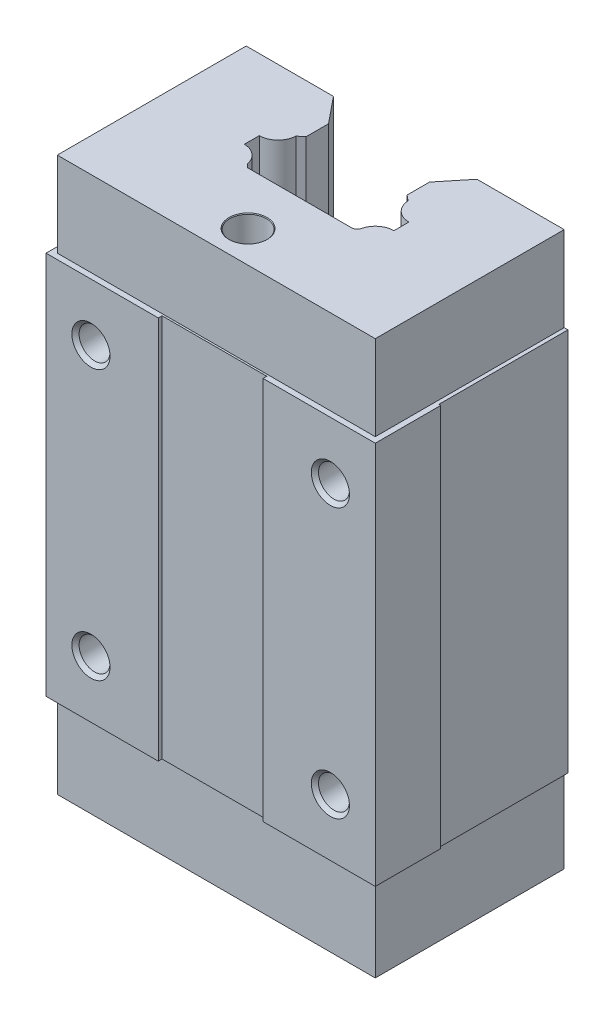
SolidWorks part; units mm, degrees
material "5086-H32, Stange (SS)"
ref_plane "Ebene vorne" through (0, 0, 0) normal (0, 0, 1) x (1, 0, 0)
ref_plane "Ebene oben" through (0, 0, 0) normal (0, 1, 0) x (1, 0, 0)
ref_plane "Ebene rechts" through (0, 0, 0) normal (1, 0, 0) x (0, 0, -1)
ref_plane "Ebene1" through (0, 0, 4) normal (0, 0, -1) x (-1, 0, 0)
sketch "Skizze1" plane through (0, 0, 4) normal (0, 0, -1) x (-1, 0, 0)
  line L0 (-22, -25.65) -> (22, -25.65)
  line L1 (22, -25.65) -> (22, 25.65)
  line L2 (22, 25.65) -> (-22, 25.65)
  line L3 (-22, 25.65) -> (-22, -25.65)
extrude "Aufsatz-Linear austragen1" add sketch "Skizze1" against normal blind 26
sketch "Skizze2" plane through (0, -25.65, 0) normal (0, -1, 0) x (1, 0, 0)
  line L0 (-21.75, 4) -> (-21.75, 21.25)
  line L1 (-21.75, 21.25) -> (-22, 21.25)
  line L2 (-22, 21.25) -> (-22, 4)
  line L3 (-22, 4) -> (-21.75, 4)
extrude "Schnitt-Linear austragen1" cut sketch "Skizze2" against normal through all
sketch "Skizze3" plane through (0, -25.65, 0) normal (0, -1, 0) x (1, 0, 0)
  line L0 (7, 30) -> (-7, 30)
  line L1 (-7, 30) -> (-7, 29.5)
  line L2 (-7, 29.5) -> (7, 29.5)
  line L3 (7, 29.5) -> (7, 30)
extrude "Schnitt-Linear austragen2" cut sketch "Skizze3" against normal through all
sketch "Skizze4" plane through (0, -25.65, 0) normal (0, -1, 0) x (1, 0, 0)
  line L0 (22, 21.25) -> (21.75, 21.25)
  line L1 (21.75, 21.25) -> (21.75, 4)
  line L2 (21.75, 4) -> (22, 4)
  line L3 (22, 4) -> (22, 21.25)
extrude "Schnitt-Linear austragen3" cut sketch "Skizze4" against normal blind 51.3
sketch "Skizze5" plane through (0, 25.65, 0) normal (0, 1, 0) x (-1, 0, 0)
  line L0 (21.25, 4) -> (-21.25, 4)
  line L1 (-21.25, 4) -> (-21.25, 29.25)
  line L2 (-21.25, 29.25) -> (21.25, 29.25)
  line L3 (21.25, 29.25) -> (21.25, 4)
extrude "Aufsatz-Linear austragen2" add sketch "Skizze5" along normal blind 11.35
sketch "Skizze6" plane through (0, -25.65, 0) normal (0, -1, 0) x (1, 0, 0)
  line L0 (21.25, 4) -> (-21.25, 4)
  line L1 (-21.25, 4) -> (-21.25, 29.25)
  line L2 (-21.25, 29.25) -> (21.25, 29.25)
  line L3 (21.25, 29.25) -> (21.25, 4)
extrude "Aufsatz-Linear austragen3" add sketch "Skizze6" along normal blind 11.35
sketch "Skizze7" plane through (0, -37, 0) normal (0, -1, 0) x (1, 0, 0)
  line L0 (-9.5938, 4) -> (9.5938, 4)
  line L1 (9.5938, 4) -> (6.75, 7.5)
  line L2 (6.75, 7.5) -> (6.75, 10.5)
  line L3 (6.75, 10.5) -> (7.5, 11.1094)
  line L4 (10, 13.5) -> (10, 15.5)
  line L5 (7.5, 18) -> (-7.5, 18)
  line L6 (-10, 15.5) -> (-10, 13.5)
  line L7 (-7.5, 11.1094) -> (-6.75, 10.5)
  line L8 (-6.75, 10.5) -> (-6.75, 7.5)
  line L9 (-6.75, 7.5) -> (-9.5938, 4)
  arc A0 (7.5, 11.1094) -> (10, 13.5) centre (10, 10.9975) cw
  arc A1 (10, 15.5) -> (7.5, 18) centre (10, 18) cw
  arc A2 (-7.5, 18) -> (-10, 15.5) centre (-10, 18) cw
  arc A3 (-10, 13.5) -> (-7.5, 11.1094) centre (-10, 10.9975) cw
extrude "Schnitt-Linear austragen4" cut sketch "Skizze7" against normal through all
hole_wizard "Bohrung1" positions "Skizze9" profile "Skizze8" legacy
sketch "Skizze9" plane through (0, -37, 0) normal (0, -1, 0) x (-1, 0, 0)
  point P0 (0, -25)
sketch "Skizze8" plane through (0, -37, 25) normal (1, 0, 0) x (0, 0, -1)
  line L0 (0, 0) -> (0, 16.4772)
  line L1 (0, 16.4772) -> (2.4585, 15)
  line L2 (2.4585, 15) -> (2.4585, 0)
  line L4 (2.4585, 0) -> (0, 0)
  line L6 (0, 16.4772) -> (-2.4585, 15) construction
  line L7 (0, -4.2442) -> (0, 117.3081) construction
  dimension "Durchmesser" = 4.917
  dimension "Tiefe" = 15
  dimension "Spitzenwinkel" = 118
hole_wizard "Bohrung2" positions "Skizze11" profile "Skizze10" legacy
sketch "Skizze11" plane through (0, 37, 0) normal (0, 1, 0) x (1, 0, 0)
  point P0 (0, -25)
sketch "Skizze10" plane through (0, 37, 25) normal (1, 0, 0) x (0, 0, 1)
  line L0 (0, 0) -> (0, 16.4772)
  line L1 (0, 16.4772) -> (2.4585, 15)
  line L2 (2.4585, 15) -> (2.4585, 0)
  line L4 (2.4585, 0) -> (0, 0)
  line L6 (0, 16.4772) -> (-2.4585, 15) construction
  line L7 (0, -4.2442) -> (0, 117.3081) construction
  dimension "Durchmesser" = 4.917
  dimension "Tiefe" = 15
  dimension "Spitzenwinkel" = 118
hole_wizard "Durchgangsloch für M3.51" positions "Skizze13" profile "Skizze12" hole size "M3.5" standard "ANSI Metrisch"
sketch "Skizze13" plane through (0, 0, 30) normal (0, 0, 1) x (1, 0, 0)
  point P0 (16, -18)
  point P1 (16, 18)
  point P2 (-16, 18)
  point P3 (-16, -18)
sketch "Skizze12" plane through (16, -18, 30) normal (1, 0, 0) x (0, -1, 0)
  line L0 (0, 0) -> (0, 7.242)
  line L1 (0, 7.242) -> (2.067, 6)
  line L2 (2.067, 6) -> (2.067, 0)
  line L5 (2.067, 0) -> (0, 0)
  line L10 (0, 7.242) -> (-2.067, 6) construction
  line L11 (0, -6.35) -> (0, 107.95) construction
  dimension "Bohrerdurchmesser" = 4.134
  dimension "Bohrungstiefe" = 6
  dimension "Spitzenwinkel" = 118
chamfer "Fase1" distance 0.483 angle 45 4 edges at (18.067, 18, 30) (-13.933, 18, 30) (18.067, -18, 30) (-13.933, -18, 30)
chamfer "Fase2" distance 0.449 angle 42.13 1 edges at (-7.5, 0, 18) first distance on face at (0, 0, 18)
chamfer "Fase3" distance 0.0915 angle 45 2 edges at (0, -37, 22.5415) (0, 37, 27.4585)
chamfer "Fase4" distance 0.449 angle 42.13 1 edges at (7.5, 0, 18) first distance on face at (0.2245, 0, 18)
